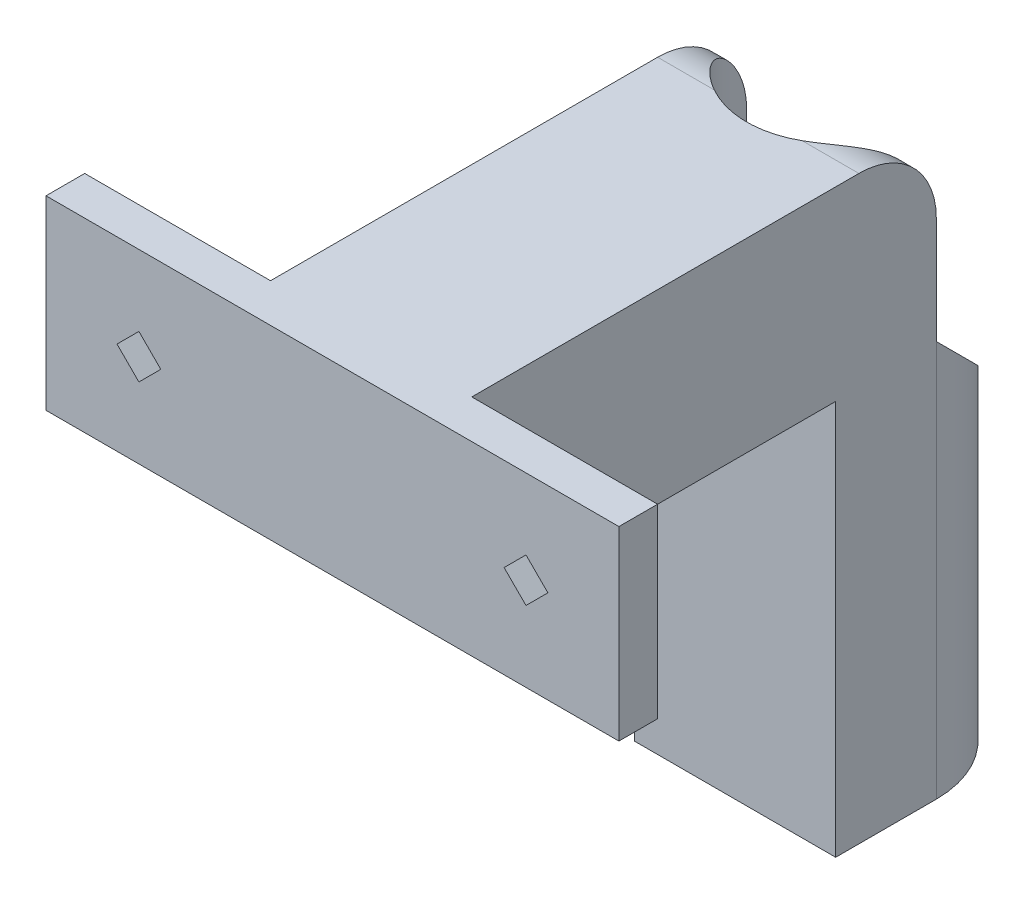
SolidWorks part; units mm, degrees
ref_plane "Front Plane" through (0, 0, 0) normal (0, 0, 1) x (1, 0, 0)
ref_plane "Top Plane" through (0, 0, 0) normal (0, 1, 0) x (1, 0, 0)
ref_plane "Right Plane" through (0, 0, 0) normal (1, 0, 0) x (0, 0, -1)
sketch "Sketch1" plane through (0, 0, 0) normal (0, 1, 0) x (1, 0, 0)
  circle A0 centre (0, 0) radius 11
  circle A1 centre (0, 0) radius 13
  dimension "D1" = 22
  dimension "D2" = 26
extrude "Boss-Extrude1" add sketch "Sketch1" along normal blind 1.2
sketch "Sketch2" plane through (0, 1.2, 0) normal (0, 1, 0) x (1, 0, 0)
  circle A0 centre (0, 0) radius 11.5
  circle A1 centre (0, 0) radius 13
  circle A2 centre (0, 0) radius 13 construction
  dimension "D1" = 23
extrude "Boss-Extrude2" add sketch "Sketch2" along normal blind 50
chamfer "Chamfer1" distance 0.5 angle 45 1 edges at (0, 1.2, 11)
sketch "Sketch3" plane through (0, 0, 0) normal (0, -1, 0) x (1, 0, 0)
  line L0 (-13, 0) -> (-13, 13)
  line L1 (-13, 13) -> (0, 13)
  line L2 (0, 13) -> (13, 13)
  line L3 (13, 13) -> (13, 0)
  line L4 (13, 0) -> (11.5, 0)
  line L5 (-13, 0) -> (-11.5, 0)
  circle A0 centre (0, 0) radius 13 construction
  circle A1 centre (0, 0) radius 11.5 construction
  arc A2 (11.5, 0) -> (-11.5, 0) centre (0, 0) ccw
  circle A3 centre (0, 0) radius 11.5 construction
  circle A4 centre (0, 0) radius 13 construction
extrude "Boss-Extrude3" add sketch "Sketch3" against normal blind 75
sketch "Sketch4" plane through (13, 0, 0) normal (1, 0, 0) x (0, 0, -1)
  line L1 (-13, 75) -> (-65, 75)
  line L2 (-13, 75) -> (-13, 51)
  line L3 (-13, 51) -> (-65, 51)
  line L4 (-65, 75) -> (-65, 51)
  dimension "D1" = 52
  dimension "D2" = 24
extrude "Boss-Extrude4" add sketch "Sketch4" against normal up to surface (26 mm away) up to face at (-13, 40.24, 5.2)
sketch "Sketch5" plane through (0, 0, 65) normal (0, 0, 1) x (1, 0, 0)
  line L0 (-13, 75) -> (-13, 51) construction
  line L1 (-13, 75) -> (-37, 75)
  line L2 (-13, 75) -> (-13, 51)
  line L3 (-13, 51) -> (-37, 51)
  line L4 (-37, 75) -> (-37, 51)
  line L5 (13, 51) -> (37, 51)
  line L6 (13, 51) -> (13, 75)
  line L7 (13, 75) -> (37, 75)
  line L8 (37, 51) -> (37, 75)
  line L9 (-13, 75) -> (13, 75) construction
  line L10 (-37, 75) -> (-13, 51) construction
  line L11 (-13, 75) -> (-37, 51) construction
  line L12 (13, 75) -> (37, 51) construction
  line L13 (37, 75) -> (13, 51) construction
  line L14 (-27.8284, 63) -> (-25, 65.8284)
  line L15 (-27.8284, 63) -> (-25, 60.1716)
  line L16 (-25, 65.8284) -> (-22.1716, 63)
  line L17 (-25, 60.1716) -> (-22.1716, 63)
  line L18 (-27.8284, 63) -> (-22.1716, 63) construction
  line L19 (-25, 65.8284) -> (-25, 60.1716) construction
  line L20 (22.1716, 63) -> (25, 65.8284)
  line L21 (22.1716, 63) -> (25, 60.1716)
  line L22 (25, 65.8284) -> (27.8284, 63)
  line L23 (25, 60.1716) -> (27.8284, 63)
  line L24 (22.1716, 63) -> (27.8284, 63) construction
  line L25 (25, 65.8284) -> (25, 60.1716) construction
  point P10 (-25, 63)
  point P15 (25, 63)
  point P16 (-25, 63)
  point P17 (25, 63)
  dimension "D1" = 24
  dimension "D2" = 24
  dimension "D3" = 4
  dimension "D4" = 4
  dimension "D5" = 4
  dimension "D6" = 4
extrude "Boss-Extrude5" add sketch "Sketch5" against normal blind 5
sketch "Sketch6" plane through (-13, 0, 0) normal (-1, 0, 0) x (0, 0, 1)
  line L0 (0, 51.2) -> (-13, 38.2)
  line L1 (-13, 51.2) -> (-13, 0) construction
  line L2 (-13, 38.2) -> (-13, 51.2)
  line L3 (-13, 51.2) -> (0, 51.2)
extrude "Cut-Extrude1" cut sketch "Sketch6" against normal through all
fillet "Fillet1" radius 10 2 edges at (12.25, 75, 0) (-12.25, 75, 0)
